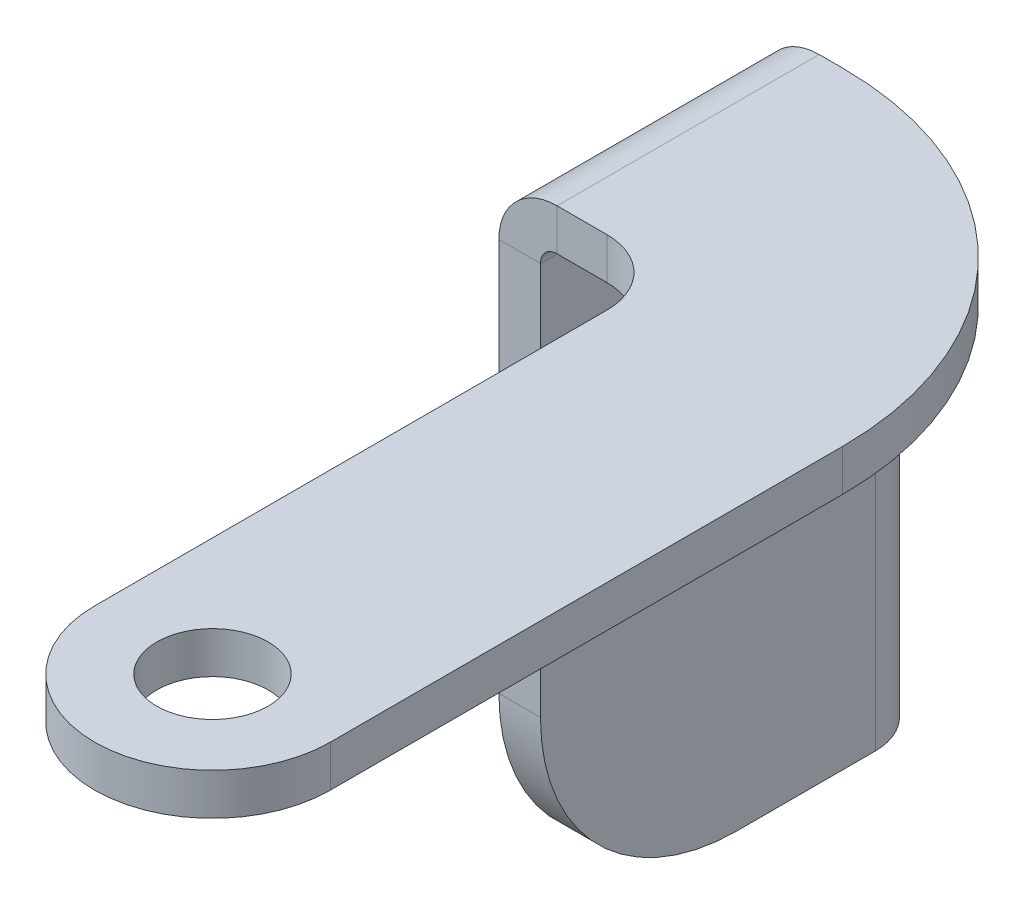
SolidWorks part; units mm, degrees
note: The reader was unsure of these and kept them because the rebuilt part matched: flange length of "Edge-Flange1", "Edge-Flange3".
material "Copper"
ref_plane "Front Plane" through (0, 0, 0) normal (0, 0, 1) x (1, 0, 0)
ref_plane "Top Plane" through (0, 0, 0) normal (0, 1, 0) x (1, 0, 0)
ref_plane "Right Plane" through (0, 0, 0) normal (1, 0, 0) x (0, 0, -1)
sketch "Sketch1" plane through (0, 0, 0) normal (0, 0, 1) x (1, 0, 0)
  line L0 (12.5, 10) -> (0, 10)
  line L1 (0, -10) -> (12.5, -10)
  line L2 (12.5, -10) -> (12.5, 10)
  circle A0 centre (0, 0) radius 4.25
  arc A1 (0, 10) -> (0, -10) centre (0, 0) ccw
  dimension "D1" = 8.5
  dimension "D2" = 10
  dimension "D3" = 12.5
base flange "Base-Flange1" sketch "Sketch1" thickness 3.175 reverse thickness direction no parameters "D1"=1.27
edge flange "Edge-Flange1" sketch "Sketch8" flange angle 90 flange length 30 flange position bend outside bend radius 1.27 thickness 3.175 relief rectangular parameters "D6"=10
sketch "Sketch8" plane through (12.5, 0, 0) normal (1, 0, 0) x (0, 1, 0)
  line L0 (-10, 0) -> (10, 0) construction
  line L1 (-10, 0) -> (10, 0)
  line L2 (-10, 0) -> (-10, 11.825)
  line L3 (5, 26.825) -> (36.2752, 26.825)
  line L5 (-10, -3.175) -> (10, -3.175) construction
  line L6 (10, 0) -> (10, 1.825)
  line L7 (15, 6.825) -> (36.2752, 6.825)
  line L8 (36.2752, 6.825) -> (36.2752, 26.825)
  line L10 (36.2752, 103.3662) -> (36.2752, 78.0596) construction
  arc A0 (10, 1.825) -> (15, 6.825) centre (15, 1.825) cw
  arc A1 (-10, 11.825) -> (5, 26.825) centre (5, 11.825) cw
  dimension "D2" = 20
  dimension "D3" = 5
  dimension "D5" = 15
  dimension "D1" = 30
bend "EdgeBend1" bend radius 1.27 bend angle 90 parameters "D5"=1
edge flange "Edge-Flange3" sketch "Sketch14" flange angle 90 flange length 31.2425 flange position material outside bend radius 1.27 thickness 3.175 relief rectangular parameters "D6"=10
sketch "Sketch14" plane through (16.945, 36.2752, 0) normal (0, -1, 0) x (0, 0, -1)
  line L2 (-26.825, 0) -> (-26.825, 5.0675)
  line L4 (-6.825, 3.0675) -> (-6.825, 0)
  line L5 (-6.825, 0) -> (-26.825, 0) construction
  line L6 (-6.825, 0) -> (-26.825, 0)
  line L7 (-31.825, 28.0675) -> (-70.9254, 28.0675)
  line L8 (-70.9254, 10.0675) -> (-31.825, 10.0675)
  arc A0 (-6.825, 3.0675) -> (-31.825, 28.0675) centre (-31.825, 3.0675) ccw
  arc A1 (-70.9254, 28.0675) -> (-70.9254, 10.0675) centre (-70.9254, 19.0675) ccw
  arc A2 (-31.825, 10.0675) -> (-26.825, 5.0675) centre (-31.825, 5.0675) cw
  circle A3 centre (-70.9254, 19.0675) radius 4.25
  dimension "D1" = 9
  dimension "D2" = 25
  dimension "D3" = 5
  dimension "D4" = 8.5
bend "EdgeBend3" bend radius 1.27 bend angle 90 parameters "D5"=2
sketch "Bend-Lines1" [suppressed] plane through (0, 0, 0) normal (0, 1, 0) x (1, 0, 0)
sketch "Bounding-Box1" [suppressed] plane through (0, 0, 0) normal (0, 1, 0) x (1, 0, 0)
sheet metal parameters "Sheet-Metal1" thickness 3.175 parameters "D1"=0.889
flat pattern "Flat-Pattern1" [suppressed]
sketch "Bend-Lines2" plane through (0, 0, 0) normal (0, 1, 0) x (1, 0, 0)
sketch3d "Bounding-Box2" [suppressed]
  line L0 (10, -10, 0) -> (-15, -10, 0) construction
  line L1 (10, 10, 0) -> (-15, 10, 0) construction
  line L2 (10, -10, 0) -> (10, 10, 0) construction
  line L3 (-15, -10, 0) -> (-15, 10, 0) construction
sheet metal parameters "Sheet-Metal2" thickness 3.175 parameters "D1"=0.889
flat pattern "Flat-Pattern1"
sketch "Bend-Lines2" plane through (0, 0, 0) normal (0, 0, 1) x (1, 0, 0)
  line L0 (16.8453, -10) -> (16.8453, 10) construction
  line L1 (16.8453, -10) -> (16.8453, 10) construction
sketch3d "Bounding-Box2" [suppressed]
  line L0 (-10, -10, 0) -> (49.2456, -10, 0) construction
  line L1 (-10, 25, 0) -> (49.2456, 25, 0) construction
  line L2 (-10, -10, 0) -> (-10, 25, 0) construction
  line L3 (49.2456, -10, 0) -> (49.2456, 25, 0) construction
bend of the flat pattern "Flatten-<EdgeBend1>1"
sheet metal parameters "Sheet-Metal4" thickness 3.175 parameters "D1"=0.889
flat pattern "Flat-Pattern1"
sketch "Bend-Lines2" plane through (0, 0, 0) normal (0, 0, 1) x (1, 0, 0)
  line L0 (14.3453, -10) -> (14.3453, 10) construction
  line L1 (14.3453, -10) -> (14.3453, 10) construction
  line L2 (41.7456, 36.8505) -> (21.7456, 36.8505) construction
  line L3 (41.7456, 36.8505) -> (21.7456, 36.8505) construction
sketch3d "Bounding-Box2" [suppressed]
  line L0 (14.7614, -28.5598, 0) -> (98.5735, 56.5944, 0) construction
  line L1 (-21.3321, 6.9649, 0) -> (62.4799, 92.1191, 0) construction
  line L2 (14.7614, -28.5598, 0) -> (-21.3321, 6.9649, 0) construction
  line L3 (98.5735, 56.5944, 0) -> (62.4799, 92.1191, 0) construction
bend of the flat pattern "Flatten-<EdgeBend1>1"
bend of the flat pattern "Flatten-<EdgeBend3>1"
